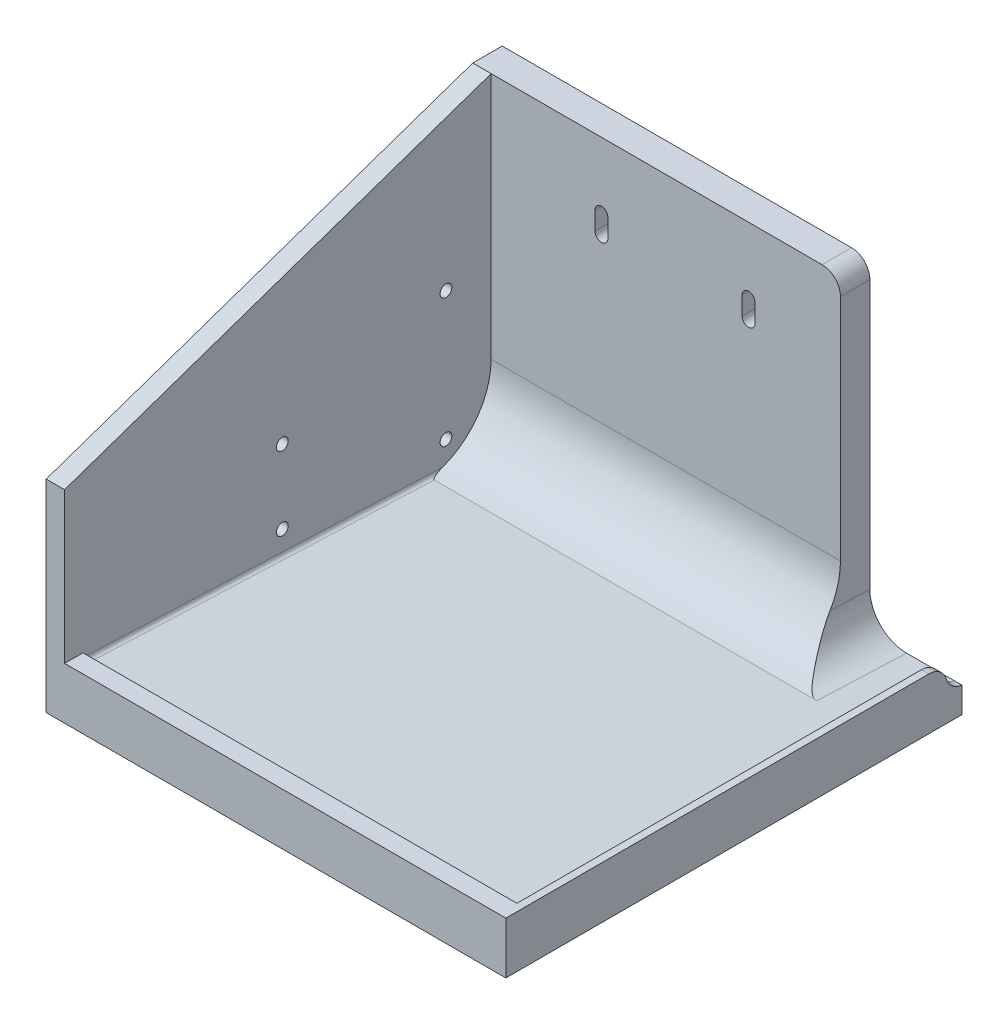
SolidWorks part; units mm, degrees
ref_plane "Front Plane" through (0, 0, 0) normal (0, 0, 1) x (1, 0, 0)
ref_plane "Top Plane" through (0, 0, 0) normal (0, 1, 0) x (1, 0, 0)
ref_plane "Right Plane" through (0, 0, 0) normal (1, 0, 0) x (0, 0, -1)
sketch "Sketch1" plane through (0, 0, 0) normal (0, 1, 0) x (1, 0, 0)
  line L0 (-48.7821, 26.8903) -> (-130, 153)
  line L1 (0, 0) -> (155, 0)
  line L2 (0, 0) -> (0, 5)
  line L3 (0, 5) -> (155, 5)
  line L4 (155, 0) -> (155, 5)
  line L5 (-130, 153) -> (-125.7963, 155.7073)
  line L6 (-125.7963, 155.7073) -> (-44.5785, 29.5976)
  line L7 (-44.5785, 29.5976) -> (-48.7821, 26.8903)
  line L8 (-44.5785, 29.5976) -> (0, 5)
  line L9 (-44.5785, 29.5976) -> (-48.7821, 26.8903)
  line L10 (0, 5) -> (0, 0)
  arc A0 (0, 0) -> (-48.7821, 26.8903) centre (0.3966, 58.4127) cw
  dimension "D1" = 130
  dimension "D3" = 150
  dimension "D4" = 58.4141
  dimension "D2" = 153
  dimension "D5" = 90
  dimension "D6" = 0
  dimension "D7" = 150
  dimension "D8" = 155
  dimension "D9" = 5
  dimension "D10" = 5
extrude "Boss-Extrude2" add sketch "Sketch1" along normal blind 55 contours L7 L6 L5 L0 | A0 L2 L8 L7 | L1 L4 L3 L2
sketch "Sketch2" plane through (0, 0, 0) normal (0, 0, 1) x (1, 0, 0)
  line L0 (0, 0) -> (155, 0) construction
  line L1 (155, 55) -> (43, 55)
  line L2 (155, 55) -> (155, 10)
  line L3 (155, 10) -> (43, 10)
  line L4 (43, 55) -> (43, 10)
  line L5 (5, 50) -> (35, 50)
  line L6 (5, 50) -> (5, 25)
  line L7 (5, 25) -> (35, 25)
  line L8 (35, 50) -> (35, 25)
  line L9 (0, 55) -> (0, 0) construction
  circle A0 centre (5, 50) radius 1.75
  circle A1 centre (35, 50) radius 1.75
  circle A2 centre (5, 25) radius 1.75
  circle A3 centre (35, 25) radius 1.75
  line M10 (155, 0) -> (155, 55)
  line M11 (155, 55) -> (0, 55)
  dimension "D6" = 3.5
  dimension "D7" = 3.5
  dimension "D8" = 3.5
  dimension "D9" = 3.5
  dimension "D2" = 25
  dimension "D3" = 25
  dimension "D4" = 30
  dimension "D5" = 5
  dimension "D10" = 10
  dimension "D11" = 8
  dimension "D12" = 8
extrude "Cut-Extrude1" cut sketch "Sketch2" against normal blind 55 contours L4 L3 M11 M10 | A2 | A0 | A1 | A3
sketch "Sketch3" plane through (-22.2397, 0, 14.3229) normal (-0.8407, 0, 0.5415) x (0.5415, 0, 0.8407)
  line L0 (-49.0207, 55) -> (-49.0207, 0) construction
  line L1 (-49.0207, 25) -> (-149.0207, 25)
  line L2 (-49.0207, 25) -> (-49.0207, 5)
  line L3 (-49.0207, 5) -> (-149.0207, 5)
  line L4 (-149.0207, 25) -> (-149.0207, 5)
  line L5 (-49.0207, 0) -> (-199.0207, 0) construction
  dimension "D1" = 5
  dimension "D2" = 20
  dimension "D3" = 100
extrude "Cut-Extrude2" cut sketch "Sketch3" against normal blind 55
sketch "Sketch4" plane through (2.115, 0, -3.833) normal (0.4831, 0, -0.8756) x (-0.8756, 0, -0.4831)
  line L6 (53.33, 25) -> (53.33, 5) construction
  line L11 (53.33, 0) -> (2.4156, 0) construction
  line L12 (8.33, 13.0659) -> (48.33, 13.0659)
  line L13 (8.33, 13.0659) -> (8.33, 5)
  line L14 (8.33, 5) -> (48.33, 5)
  line L15 (48.33, 13.0659) -> (48.33, 5)
  dimension "D1" = 5
  dimension "D2" = 40
  dimension "D3" = 5
extrude "Cut-Extrude3" cut sketch "Sketch4" against normal blind 55
sketch "Sketch5" plane through (0, 0, 0) normal (0, -1, 0) x (1, 0, 0)
  line L0 (0, -5) -> (-44.5785, -29.5976)
  line L2 (0, -5) -> (0, -155.7073)
  line L3 (0, -155.7073) -> (-125.7963, -155.7073)
  line L5 (-44.5785, -29.5976) -> (0, -5) construction
  line L6 (-44.5785, -29.5976) -> (-125.7963, -155.7073)
extrude "Boss-Extrude4" add sketch "Sketch5" against normal blind 5
sketch "Sketch8" plane through (0, 5, 0) normal (0, 1, 0) x (1, 0, 0)
  line L5 (-44.5785, 29.5976) -> (-98.7237, 113.6707)
  line L7 (-44.5785, 29.5976) -> (-44.5785, 113.6707)
  line L8 (-44.5785, 113.6707) -> (-98.7237, 113.6707)
extrude "Cut-Extrude4" cut sketch "Sketch8" against normal blind 50
sketch "Sketch9" plane through (0, 5, 0) normal (0, 1, 0) x (1, 0, 0)
  line L1 (-40.2007, 27.182) -> (-44.5785, 27.182)
  line L2 (-40.2007, 27.182) -> (-40.2007, 113.6707)
  line L3 (-40.2007, 113.6707) -> (-44.5785, 113.6707)
  line L4 (-44.5785, 27.182) -> (-44.5785, 113.6707)
extrude "Boss-Extrude7" add sketch "Sketch9" along normal blind 50
sketch "Sketch10" plane through (0, 5, 0) normal (0, 1, 0) x (1, 0, 0)
  line L1 (-40.2007, 113.6707) -> (-20.2007, 113.6707)
  line L2 (-40.2007, 113.6707) -> (-40.2007, 27.1384)
  line L3 (-40.2007, 27.1384) -> (-20.2007, 27.1384)
  line L4 (-20.2007, 113.6707) -> (-20.2007, 27.1384)
  dimension "D1" = 20
extrude "Cut-Extrude5" cut sketch "Sketch10" against normal blind 10
sketch "Sketch12" plane through (-40.2007, 0, 0) normal (1, 0, 0) x (0, 0, -1)
  line L6 (27.182, 5) -> (27.182, 13.0659) construction
  circle A0 centre (57.182, 10) radius 9.5
  circle A1 centre (77.182, 10) radius 6
  dimension "D4" = 19
  dimension "D5" = 12
  dimension "D1" = 30
  dimension "D3" = 20
extrude "Cut-Extrude6" cut sketch "Sketch12" against normal blind 10
sketch "Sketch13" plane through (-40.2007, 0, 0) normal (1, 0, 0) x (0, 0, -1)
  circle A0 centre (57.182, 10) radius 9.5
  circle A1 centre (77.182, 10) radius 6
  circle A2 centre (57.182, 10) radius 9.5 construction
  circle A3 centre (77.182, 10) radius 6 construction
  dimension "D1" = 0
  dimension "D2" = 0
  dimension "D3" = 19
  dimension "D4" = 12
extrude "Cut-Extrude7" cut sketch "Sketch13" along normal blind 50
sketch "Sketch14" plane through (0, 5, 0) normal (0, 1, 0) x (1, 0, 0)
  line L0 (0, 103.0381) -> (-91.876, 103.0381)
  line L1 (0, 155.7073) -> (-126.1063, 155.7073)
  line L2 (0, 155.7073) -> (0, 103.0381)
  line L5 (-98.7237, 113.6707) -> (-125.7963, 155.7073) construction
  line L6 (-91.876, 103.0381) -> (-126.1063, 155.7073)
extrude "Cut-Extrude8" cut sketch "Sketch14" against normal blind 50
sketch "Sketch15" plane through (-22.2397, 0, 14.3229) normal (-0.8407, 0, 0.5415) x (0.5415, 0, 0.8407)
  line L0 (-176.0359, 0) -> (-199.0207, 18.2475)
  line L1 (-199.0207, 0) -> (-176.0359, 0)
  line L2 (-199.0207, 0) -> (-199.0207, 18.2475)
extrude "Cut-Extrude9" cut sketch "Sketch15" against normal blind 50
sketch "Sketch16" plane through (-40.2007, 0, 0) normal (1, 0, 0) x (0, 0, -1)
  line L0 (113.6707, 15.4952) -> (48.2529, 55)
  line L1 (113.6707, 55) -> (113.6707, 5) construction
  line L2 (27.182, 55) -> (113.6707, 55) construction
  line L3 (48.2529, 55) -> (113.6707, 55)
  line L4 (113.6707, 55) -> (113.6707, 15.4952)
extrude "Cut-Extrude10" cut sketch "Sketch16" against normal blind 10
fillet "Fillet5" radius 3 4 edges at (-100.8476, 5, -112.3029) (-46.6803, 5, -28.2439) (-100.8255, 25, -112.3171) (-46.6803, 25, -28.2439)
sketch "Sketch18" plane through (0, 5, 0) normal (0, 1, 0) x (1, 0, 0)
  line L1 (0, 103.0381) -> (-98.7678, 103.0381)
  line L2 (0, 103.0381) -> (0, 113.6423)
  line L3 (0, 113.6423) -> (-98.7678, 113.6423)
  line L4 (-98.7678, 103.0381) -> (-98.7678, 113.6423)
extrude "Boss-Extrude8" add sketch "Sketch18" against normal blind 5
sketch "Sketch19" plane through (0, 0, 0) normal (0, -1, 0) x (1, 0, 0)
  line L0 (-97.8232, -103.0381) -> (-98.7678, -104.5048)
  line L5 (-98.7678, -104.5048) -> (-98.7678, -103.0381)
  line L6 (-98.7678, -104.5048) -> (-98.7678, -103.0381) construction
  line L7 (-98.7678, -103.0381) -> (-97.8232, -103.0381)
extrude "Cut-Extrude11" cut sketch "Sketch19" against normal blind 5 contours L0 L5 L7
sketch "Sketch20" plane through (0, 0, 0) normal (0, -1, 0) x (1, 0, 0)
  line L1 (0, -5) -> (155, -5)
  line L2 (0, -5) -> (0, -124)
  line L3 (0, -124) -> (155, -124)
  line L4 (155, -5) -> (155, -124)
  dimension "D1" = 119
  dimension "D2" = 155
extrude "Boss-Extrude9" add sketch "Sketch20" against normal blind 10
sketch "Sketch21" plane through (155, 0, 0) normal (1, 0, 0) x (0, 0, -1)
  line L1 (124, 10) -> (0, 10) construction
  line L4 (5, 10) -> (124, 10)
  line L5 (124, 10) -> (124, 7)
  line L6 (124, 7) -> (5, 10)
  line L7 (124, 10) -> (124, 0) construction
  dimension "D1" = 5
  dimension "D2" = 0
  dimension "D3" = 3
extrude "Cut-Extrude13" cut sketch "Sketch21" against normal blind 155
sketch "Sketch24" plane through (0, 0, 0) normal (0, -1, 0) x (1, 0, 0)
  line L0 (0, -124) -> (155, -124) construction
  line L1 (125, -124) -> (0, -124)
  line L2 (125, -124) -> (125, -116)
  line L3 (125, -116) -> (0, -116)
  line L4 (0, -124) -> (0, -116)
  line L5 (155, 0) -> (155, -124) construction
  line L6 (0, -5) -> (0, -124) construction
  dimension "D1" = 30
  dimension "D2" = 0
  dimension "D3" = 8
extrude "Boss-Extrude10" add sketch "Sketch24" against normal blind 95
fillet "Fillet6" radius 20 1 edges at (62.5, 7.2017, -116)
sketch "Sketch25" plane through (0, 0, -124) normal (0, 0, -1) x (-1, 0, 0)
  line L0 (-33.25, 77) -> (-33.25, 72)
  line L6 (-125, 95) -> (0, 95) construction
  line L10 (-36.75, 77) -> (-36.75, 72)
  line L11 (-73.25, 77) -> (-73.25, 72)
  line L12 (-76.75, 77) -> (-76.75, 72)
  line L14 (0, 95) -> (0, 0) construction
  arc A4 (-36.75, 77) -> (-33.25, 77) centre (-35, 77) cw
  arc A5 (-73.25, 72) -> (-76.75, 72) centre (-75, 72) cw
  arc A6 (-73.25, 77) -> (-76.75, 77) centre (-75, 77) ccw
  arc A7 (-36.75, 72) -> (-33.25, 72) centre (-35, 72) ccw
  arc A8 (-33.25, 77) -> (-36.75, 77) centre (-35, 77) ccw
  dimension "D4" = 40
  dimension "D6" = 40
  dimension "D1" = 23
  dimension "D2" = 23
  dimension "D3" = 5
  dimension "D8" = 35
  dimension "D9" = 35
sketch "Sketch26" plane through (2.115, 0, -3.833) normal (0.4831, 0, -0.8756) x (-0.8756, 0, -0.4831)
  line L0 (48.33, 13.0659) -> (8.33, 13.0659) construction
  line L1 (36.33, 13.0659) -> (20.33, 13.0659)
  line L2 (36.33, 13.0659) -> (36.33, 14.5659)
  line L3 (36.33, 14.5659) -> (20.33, 14.5659)
  line L4 (20.33, 13.0659) -> (20.33, 14.5659)
  line L5 (8.33, 13.0659) -> (8.33, 5) construction
  line L6 (48.33, 55) -> (48.33, 13.0659) construction
  dimension "D1" = 12
  dimension "D2" = 12
  dimension "D3" = 16
  dimension "D4" = 1.5
extrude "Boss-Extrude11" add sketch "Sketch26" along normal blind 12
sketch "Sketch27" plane through (0, 14.5659, 0) normal (0, 1, 0) x (1, 0, 0)
  line L0 (-15.6851, 13.6547) -> (-9.8877, 24.1614)
  line L1 (-9.8877, 24.1614) -> (-23.8966, 31.8913)
  line L2 (-23.8966, 31.8913) -> (-29.694, 21.3846)
  line L3 (-29.694, 21.3846) -> (-28.0304, 20.4667)
  line L4 (-29.694, 21.3846) -> (-15.6851, 13.6547) construction
  line L5 (-28.0304, 20.4667) -> (-23.151, 29.3098)
  line L6 (-23.151, 29.3098) -> (-12.4692, 23.4158)
  line L7 (-12.4692, 23.4158) -> (-17.3486, 14.5727)
  line L8 (-17.3486, 14.5727) -> (-15.6851, 13.6547)
  dimension "D1" = 1.9
  dimension "D2" = 1.9
  dimension "D3" = 1.9
extrude "Boss-Extrude12" add sketch "Sketch27" along normal blind 15
sketch "Sketch28" plane through (0, 14.5659, 0) normal (0, 1, 0) x (1, 0, 0)
  circle A0 centre (-20.2498, 21.9412) radius 2.5
  dimension "D1" = 5
extrude "Cut-Extrude15" cut sketch "Sketch28" against normal blind 5
extrude "Cut-Extrude17" cut sketch "Sketch25" against normal blind 35 contours L10 A7 L0 A4 | L11 A6 L12 A5
sketch "Sketch29" plane through (0, 0, 0) normal (0, 0, 1) x (1, 0, 0)
  line L1 (43, 55) -> (0, 55)
  line L6 (0, 12) -> (43, 12)
  line L7 (0, 12) -> (0, 55)
  line L8 (43, 55) -> (43, 12)
extrude "Cut-Extrude18" cut sketch "Sketch29" against normal blind 35
fillet "Fillet9" radius 10 5 edges at (-127.8982, 55, -154.3536) (-115.5221, 0, -134.985) (-127.8982, 18.2475, -154.3536) (-42.3896, 15.4952, -113.6707) (-42.3896, 55, -48.2529)
sketch "Sketch31" plane through (155, 0, 0) normal (1, 0, 0) x (0, 0, -1)
  line L0 (124, 7) -> (124, 0) construction
  line L1 (0, 0) -> (124, 0)
  line L2 (0, 0) -> (0, 12)
  line L3 (0, 12) -> (124, 12)
  line L4 (124, 0) -> (124, 12)
  dimension "D1" = 0
  dimension "D2" = 12
extrude "Boss-Extrude14" add sketch "Sketch31" against normal blind 2
sketch "Sketch32" plane through (153, 0, 0) normal (-1, 0, 0) x (0, 0, 1)
  line L0 (-124, 12) -> (0, 12) construction
  line L1 (0, 10) -> (-5, 10)
  line L2 (0, 10) -> (0, 12)
  line L3 (0, 12) -> (-5, 12)
  line L4 (-5, 10) -> (-5, 12)
  dimension "D1" = 5
  dimension "D2" = 2
extrude "Boss-Extrude15" add sketch "Sketch32" along normal blind 132
sketch "Sketch33" plane through (0, 0, 0) normal (0, 0, 1) x (1, 0, 0)
  line L0 (0, 0) -> (155, 0) construction
  line L1 (155, 12) -> (135, 12)
  line L2 (155, 12) -> (155, 0)
  line L3 (155, 0) -> (135, 0)
  line L4 (135, 12) -> (135, 0)
  dimension "D1" = 20
extrude "Cut-Extrude19" cut sketch "Sketch33" against normal blind 160
sketch "Sketch34" plane through (0, 0, 0) normal (0, 0, 1) x (1, 0, 0)
  line L0 (0, 0) -> (135, 0) construction
  line L1 (135, 12) -> (133, 12)
  line L2 (135, 12) -> (135, 0)
  line L3 (135, 0) -> (133, 0)
  line L4 (133, 12) -> (133, 0)
  dimension "D1" = 2
extrude "Boss-Extrude17" add sketch "Sketch34" against normal blind 123
sketch "Sketch36" plane through (-40.2007, 0, 0) normal (1, 0, 0) x (0, 0, -1)
  line L0 (103.0381, 0) -> (27.1384, 0) construction
  circle A0 centre (90.1949, 10) radius 6
  dimension "D1" = 12
  dimension "D2" = 10
extrude "Cut-Extrude20" cut sketch "Sketch36" against normal mid plane 80
sketch "Sketch38" plane through (125, 0, 0) normal (1, 0, 0) x (0, 0, -1)
  line L0 (95.496, 7.7186) -> (124, 7)
  line L1 (124, 7) -> (124, 95)
  line L2 (124, 95) -> (116, 95)
  line L3 (116, 95) -> (95.496, 7.7186)
extrude "Cut-Extrude21" cut sketch "Sketch38" against normal blind 25
sketch "Sketch39" plane through (0, 0, 0) normal (0, 0, 1) x (1, 0, 0)
  line L0 (0, 0) -> (135, 0) construction
  line L1 (135, 12) -> (125, 12)
  line L2 (135, 12) -> (135, 0)
  line L3 (135, 0) -> (125, 0)
  line L4 (125, 12) -> (125, 0)
  dimension "D1" = 10
extrude "Cut-Extrude22" cut sketch "Sketch39" against normal blind 165
sketch "Sketch40" plane through (0, 0, 0) normal (0, 0, 1) x (1, 0, 0)
  line L6 (0, 0) -> (125, 0) construction
  line L7 (125, 12) -> (123, 12)
  line L8 (125, 12) -> (125, 0)
  line L9 (125, 0) -> (123, 0)
  line L10 (123, 12) -> (123, 0)
  point P6 (0, 0)
  dimension "D1" = 2
extrude "Boss-Extrude18" add sketch "Sketch40" against normal blind 115
sketch "Sketch41" plane through (0, 5, 0) normal (0, 1, 0) x (1, 0, 0)
  line L0 (-20.2007, 49.1042) -> (0, 49.1042) construction
  line L1 (0, 113.6423) -> (-5, 113.6423)
  line L2 (0, 113.6423) -> (0, 49.1042)
  line L3 (0, 49.1042) -> (-5, 49.1042)
  line L4 (-5, 113.6423) -> (-5, 49.1042)
  dimension "D1" = 5
extrude "Boss-Extrude19" add sketch "Sketch41" against normal blind 5
sketch "Sketch42" plane through (0, 5, 0) normal (0, 1, 0) x (1, 0, 0)
  line L4 (-5, 124) -> (-5, 0)
  line L5 (-5, 0) -> (5, 0)
  line L9 (5, 0) -> (5, 124)
  line L10 (-5, 124) -> (5, 124)
  line L11 (0, 124) -> (125, 124) construction
  line L12 (0, 0) -> (125, 0) construction
  dimension "D1" = 0
  dimension "D2" = 124
extrude "Boss-Extrude20" add sketch "Sketch42" along normal up to surface (90 mm away) up to face at (50, 95, -120)
sketch "Sketch45" plane through (5, 0, 0) normal (1, 0, 0) x (0, 0, -1)
  line L1 (5, 10) -> (95.496, 7.7186) construction
  circle A0 centre (59.2085, 36.1358) radius 1.6
  circle A1 centre (59.2085, 16.1358) radius 1.6
  circle A2 centre (103.7183, 50.0137) radius 1.6
  circle A3 centre (103.7183, 15.0137) radius 1.6
  dimension "D5" = 3.2
  dimension "D6" = 3.2
  dimension "D7" = 3.2
  dimension "D8" = 3.2
  dimension "D3" = 7.5
  dimension "D1" = 35
  dimension "D2" = 7.5
  dimension "D4" = 20
extrude "Cut-Extrude23" cut sketch "Sketch45" against normal blind 30
sketch "Sketch46" plane through (0, 0, 0) normal (0, 0, 1) x (1, 0, 0)
  line L1 (0, 0) -> (-157.5557, 0)
  line L2 (0, 0) -> (0, 97.6171)
  line L3 (0, 97.6171) -> (-157.5557, 97.6171)
  line L4 (-157.5557, 0) -> (-157.5557, 97.6171)
extrude "Cut-Extrude24" cut sketch "Sketch46" against normal blind 160
sketch "Sketch51" plane through (125, 0, 0) normal (1, 0, 0) x (0, 0, -1)
  line L0 (124, 7) -> (5, 12)
  line L1 (5, 12) -> (5, 14.0956)
  line L2 (5, 14.0956) -> (0, 14.0956)
  line L3 (0, 14.0956) -> (0, 7.1134)
  line L4 (0, 12) -> (0, 0) construction
  line L5 (0, 7.1134) -> (124, 7)
extrude "Boss-Extrude22" add sketch "Sketch51" against normal blind 120
sketch "Sketch52" plane through (0, 0, 0) normal (0, 0, 1) x (1, 0, 0)
  line L0 (0, 0) -> (125, 0) construction
  line L1 (125, 14.0956) -> (123, 14.0956)
  line L2 (125, 14.0956) -> (125, 0)
  line L3 (125, 0) -> (123, 0)
  line L4 (123, 14.0956) -> (123, 0)
  dimension "D1" = 2
extrude "Boss-Extrude23" add sketch "Sketch52" against normal blind 120
sketch "Sketch54" plane through (5, 0, 0) normal (1, 0, 0) x (0, 0, -1)
  line L0 (0, 55) -> (116, 95)
  line L1 (116, 95) -> (0, 95)
  line L2 (0, 95) -> (0, 55)
  line L3 (0, 95) -> (0, 14.0956) construction
  point P0 (0, 45.0013)
  point P4 (0, 0)
  point P9 (-0.7822, 14.0956)
  dimension "D1" = 55
fillet "Fillet14" radius 10 1 edges at (100, 7.5139, -111.7693)
fillet "Fillet15" radius 5 1 edges at (124, 14.0956, -120)
fillet "Fillet16" radius 5 1 edges at (124, 7.1681, -120)
fillet "Fillet17" radius 5 1 edges at (100, 95, -120)
fillet "Fillet18" radius 1 1 edges at (5, 10.0139, -52.2693)
extrude "Cut-Extrude27" cut sketch "Sketch54" against normal blind 30
